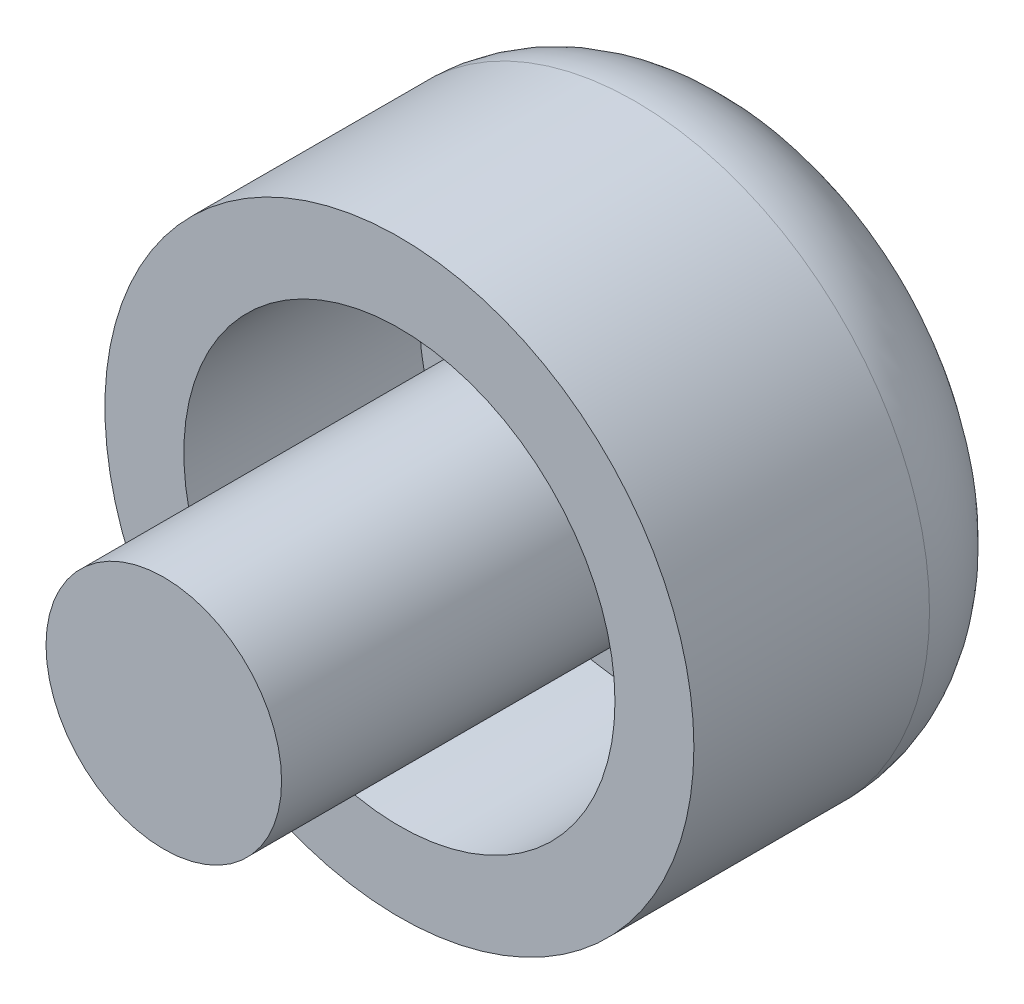
SolidWorks part; units mm, degrees
ref_plane "前视基准面" through (0, 0, 0) normal (0, 0, 1) x (1, 0, 0)
ref_plane "上视基准面" through (0, 0, 0) normal (0, 1, 0) x (1, 0, 0)
ref_plane "右视基准面" through (0, 0, 0) normal (1, 0, 0) x (0, 0, -1)
other "Configuration Table"
sketch "草图1" plane through (0, 0, 0) normal (0, 0, 1) x (1, 0, 0)
  circle A0 centre (0, 0) radius 5
  dimension "D1" = 10
extrude "凸台-拉伸1" add sketch "草图1" along normal blind 20
sketch "草图2" plane through (0, 0, 0) normal (0, 0, -1) x (-1, 0, 0)
  circle A0 centre (0, 0) radius 12.5
  dimension "D1" = 25
extrude "凸台-拉伸2" add sketch "草图2" along normal blind 5
sketch "草图3" plane through (0, 0, 0) normal (0, 0, 1) x (1, 0, 0)
  circle A0 centre (0, 0) radius 9.15
  circle A1 centre (0, 0) radius 12.5
  dimension "D1" = 25
  dimension "D2" = 18.3
extrude "凸台-拉伸3" add sketch "草图3" along normal blind 10
fillet "圆角1" radius 5 1 edges at (-12.5, 0, -5)
